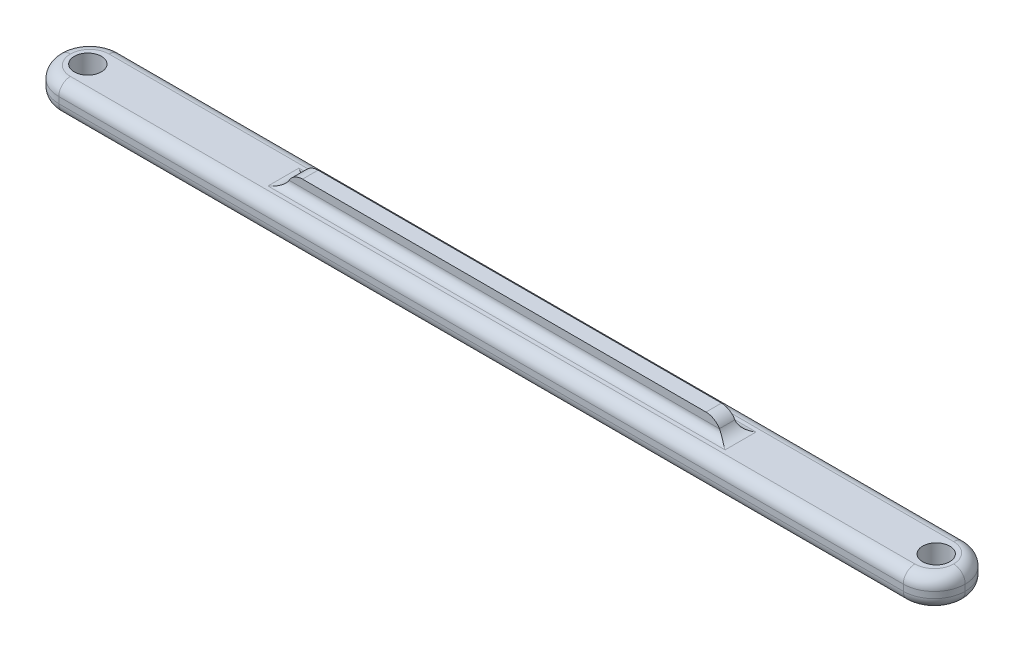
SolidWorks part; units mm, degrees
material "ABS"
ref_plane "Front Plane" through (0, 0, 0) normal (0, 0, 1) x (1, 0, 0)
ref_plane "Top Plane" through (0, 0, 0) normal (0, 1, 0) x (1, 0, 0)
ref_plane "Right Plane" through (0, 0, 0) normal (1, 0, 0) x (0, 0, -1)
sketch "Sketch1" plane through (0, 0, 0) normal (0, 1, 0) x (1, 0, 0)
  line L1 (-58.5, 4) -> (58.5, 4)
  line L2 (-58.5, 4) -> (-58.5, -4)
  line L3 (-58.5, -4) -> (58.5, -4)
  line L4 (58.5, 4) -> (58.5, -4)
  line L5 (-58.5, 4) -> (58.5, -4) construction
  line L6 (-58.5, -4) -> (58.5, 4) construction
  point P0 (0, 0)
  dimension "D1" = 8
  dimension "D2" = 117
extrude "Boss-Extrude1" add sketch "Sketch1" along normal blind 3.8
sketch "Sketch2" plane through (0, 3.8, 0) normal (0, 1, 0) x (1, 0, 0)
  line L0 (0, 0) -> (-54.75, 0) construction
  line L1 (0, 0) -> (54.75, 0) construction
  line L3 (-58.5, 4) -> (-58.5, -4) construction
  line L4 (58.5, -4) -> (58.5, 4) construction
  circle A0 centre (-54.75, 0) radius 1.75
  circle A1 centre (54.75, 0) radius 1.75
  dimension "D3" = 3.5
  dimension "D4" = 3.5
  dimension "D1" = 3.75
  dimension "D2" = 3.75
extrude "Cut-Extrude4" cut sketch "Sketch2" against normal through all
fillet "Fillet1" radius 4 4 edges at (58.5, 1.9, -4) (58.5, 1.9, 4) (-58.5, 1.9, 4) (-58.5, 1.9, -4)
fillet "Fillet2" radius 1.5 12 edges at (57.3284, 0, -2.8284) (57.3284, 0, 2.8284) (0, 0, 4) (-57.3284, 0, 2.8284) (-57.3284, 0, -2.8284) (57.3284, 3.8, -2.8284) (57.3284, 3.8, 2.8284) (0, 3.8, 4) (-57.3284, 3.8, 2.8284) (-57.3284, 3.8, -2.8284) (0, 0, -4) (0, 3.8, -4)
sketch "Sketch3" plane through (0, 3.8, 0) normal (0, 1, 0) x (1, 0, 0)
  line L1 (-27.5, 1) -> (27.5, 1)
  line L2 (-27.5, 1) -> (-27.5, -1)
  line L3 (-27.5, -1) -> (27.5, -1)
  line L4 (27.5, 1) -> (27.5, -1)
  line L5 (-27.5, 1) -> (27.5, -1) construction
  line L6 (-27.5, -1) -> (27.5, 1) construction
  point P0 (0, 0)
  dimension "D1" = 55
  dimension "D2" = 2
extrude "Boss-Extrude2" add sketch "Sketch3" along normal blind 2 and the other way blind 5.8
fillet "Fillet3" radius 2 4 edges at (-27.5, 0, 0) (27.5, 0, 0) (-27.5, 3.8, 0) (27.5, 3.8, 0)
fillet "Fillet4" radius 2 4 edges at (-27.5, 5.8, 0) (-27.5, -2, 0) (27.5, -2, 0) (27.5, 5.8, 0)
fillet "Fillet5" radius 1 4 edges at (0, 3.8, -1) (0, 3.8, 1) (0, 0, 1) (0, 0, -1)
